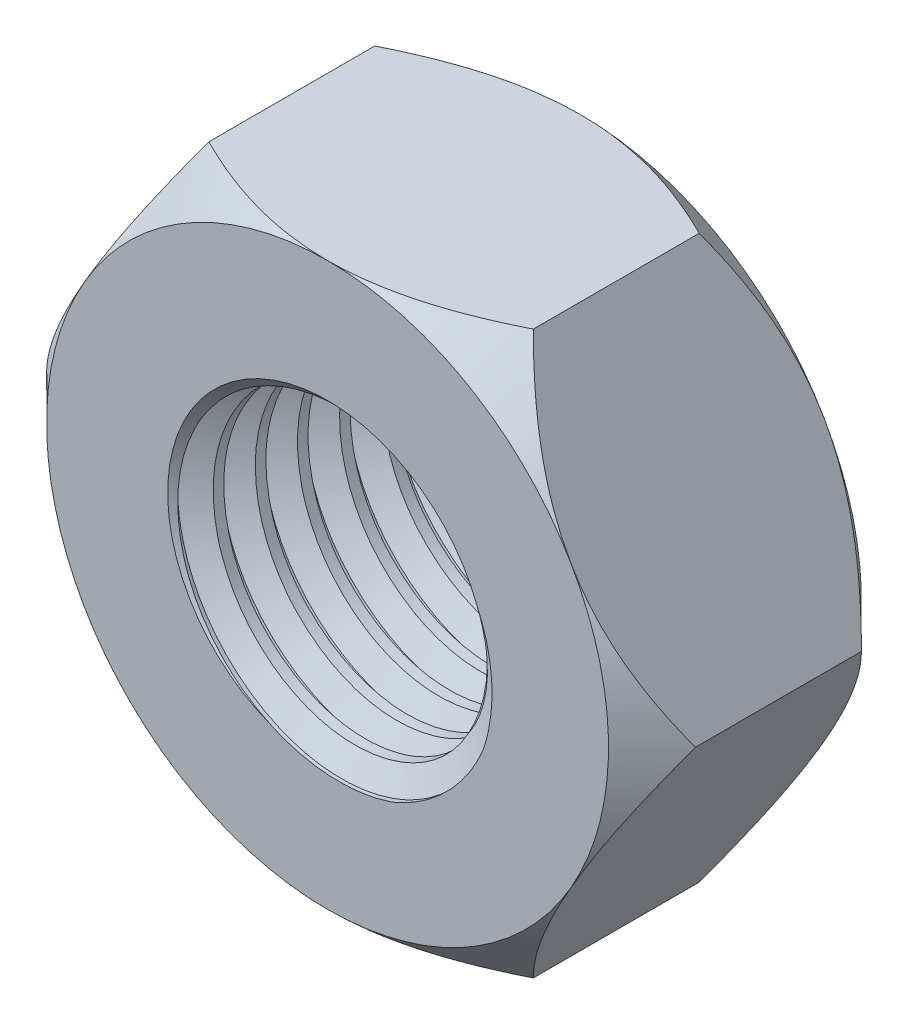
SolidWorks part; units mm, degrees
ref_plane "Front Plane" through (0, 0, 0) normal (0, 0, 1) x (1, 0, 0)
ref_plane "Top Plane" through (0, 0, 0) normal (0, 1, 0) x (1, 0, 0)
ref_plane "Right Plane" through (0, 0, 0) normal (1, 0, 0) x (0, 0, -1)
sketch "Sketch1" plane through (0, 0, 0) normal (0, 0, 1) x (1, 0, 0)
  line L1 (-11.547, 0) -> (-5.7735, -10)
  line L2 (-5.7735, -10) -> (5.7735, -10)
  line L3 (5.7735, -10) -> (11.547, 0)
  line L4 (11.547, 0) -> (5.7735, 10)
  line L5 (5.7735, 10) -> (-5.7735, 10)
  line L6 (-5.7735, 10) -> (-11.547, 0)
  circle A0 centre (0, 0) radius 10 construction
  dimension "D1" = 20
extrude "Boss-Extrude1" add sketch "Sketch1" along normal mid plane 9
sketch "Sketch2" plane through (0, 0, 4.5) normal (0, 0, 1) x (1, 0, 0)
  line L0 (-5.7735, 10) -> (-11.547, 0) construction
  circle A0 centre (0, 0) radius 10
extrude "Cut-Extrude1" cut sketch "Sketch2" against normal through all draft 45 flip side to cut
mirror "Mirror1" about plane through (0, 0, 0) normal (0, 0, 1) of "Cut-Extrude1"
sketch "Sketch3" plane through (0, 0, 4.5) normal (0, 0, 1) x (1, 0, 0)
  circle A0 centre (0, 0) radius 5.19
  dimension "D1" = 10.38
extrude "Cut-Extrude2" cut sketch "Sketch3" against normal through all
chamfer "Chamfer1" distance 0.5 angle 45 2 edges at (5.19, 0, -4.5) (5.19, 0, 4.5)
thread "Thread1" pitch 1.5 method cut profile "Thread Profile1" start angle 0, offset 2, length 0, pitch 1.5, diameter 10.38
ref_plane "Plane1" through (-5.19, 0, 6) normal (0, -1, 0) x (-1, 0, 0)
sketch "Thread Profile1" plane through (-5.19, 0, 6) normal (0, -1, 0) x (-1, 0, 0)
  line L0 (0, 0) -> (0, 1.5) construction
  line L1 (0, 0) -> (0.8119, 0.4687)
  line L2 (0.8119, 0.4687) -> (0.8119, 0.6562)
  line L3 (0.8119, 0.6562) -> (0, 1.125)
  line L4 (0.8119, 0.5625) -> (0, 0.5625) construction
  line L11 (0, 0) -> (0, 1.125)
  point P2 (0, 0)
  dimension "Pitch" = 1.5
  dimension "Profile_Angle" = 60
  dimension "Profile_Land" = 0.1875
  dimension "Profile_Height" = 0.8119
